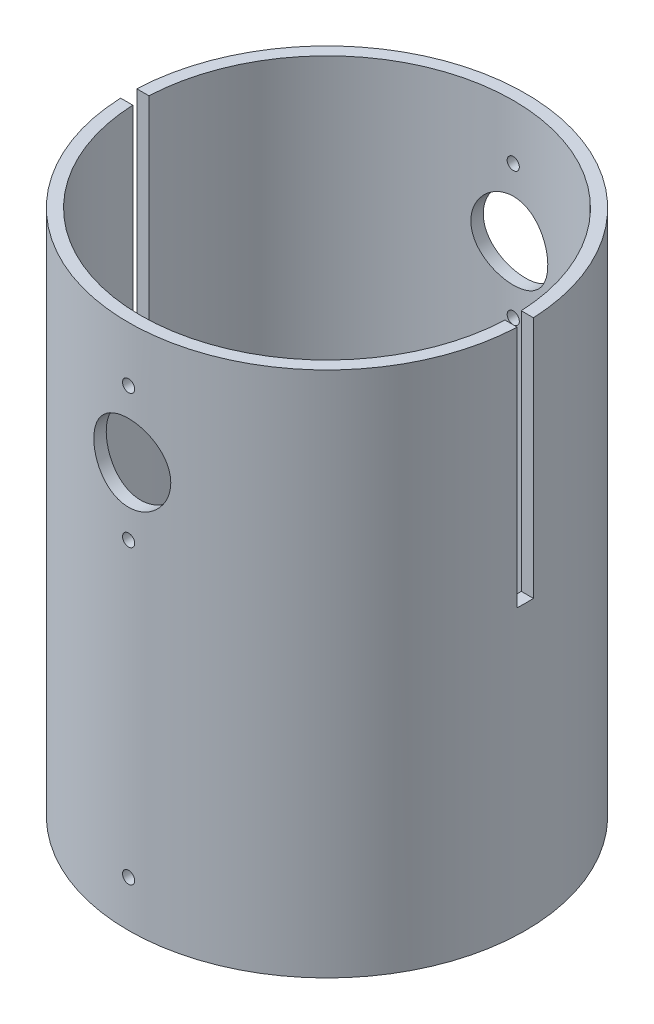
SolidWorks part; units mm, degrees
ref_plane "Front Plane" through (0, 0, 0) normal (0, 0, 1) x (1, 0, 0)
ref_plane "Top Plane" through (0, 0, 0) normal (0, 1, 0) x (1, 0, 0)
ref_plane "Right Plane" through (0, 0, 0) normal (1, 0, 0) x (0, 0, -1)
sketch "Sketch1" plane through (0, 0, 0) normal (0, 1, 0) x (1, 0, 0)
  circle A0 centre (0, 0) radius 46
  circle A1 centre (0, 0) radius 49
  dimension "D1" = 92
  dimension "D2" = 98
extrude "Boss-Extrude1" add sketch "Sketch1" along normal blind 130
sketch "Sketch2" plane through (0, 0, 0) normal (0, 0, 1) x (1, 0, 0)
  line L0 (0, 0) -> (0, 11.4) construction
  circle A0 centre (0, 11.4) radius 1.5
  dimension "D2" = 3
  dimension "D1" = 11.4
extrude "Cut-Extrude1" cut sketch "Sketch2" against normal through all and the other way through all
sketch "Sketch3" plane through (0, 0, 0) normal (0, 0, 1) x (1, 0, 0)
  line L0 (0, 130) -> (0, 100) construction
  line L1 (46, 130) -> (-46, 130) construction
  circle A0 centre (0, 100) radius 9.5
  dimension "D2" = 19
  dimension "D1" = 30
extrude "Cut-Extrude2" cut sketch "Sketch3" against normal through all and the other way through all
sketch "Sketch4" plane through (0, 0, 0) normal (0, 0, 1) x (1, 0, 0)
  line L0 (0, 100) -> (0, 83.5) construction
  line L1 (0, 83.5) -> (0, 100) construction
  line L2 (0, 100) -> (13.5459, 100) construction
  circle A0 centre (0, 83.5) radius 1.5
  circle A1 centre (0, 116.5) radius 1.5
  dimension "D2" = 3
  dimension "D1" = 16.5
extrude "Cut-Extrude3" cut sketch "Sketch4" against normal through all and the other way through all
sketch "Sketch5" plane through (0, 0, 0) normal (1, 0, 0) x (0, 0, -1)
  line L0 (0, 130) -> (0, 70) construction
  line L1 (46, 130) -> (-46, 130) construction
  line L2 (0, 70) -> (2, 70)
  line L3 (2, 70) -> (2, 130)
  line L4 (2, 130) -> (-2, 130)
  line L5 (-2, 130) -> (-2, 70)
  line L6 (-2, 70) -> (0, 70)
  dimension "D1" = 60
  dimension "D2" = 2
  dimension "D3" = 4
extrude "Cut-Extrude4" cut sketch "Sketch5" against normal blind 70 and the other way blind 70
